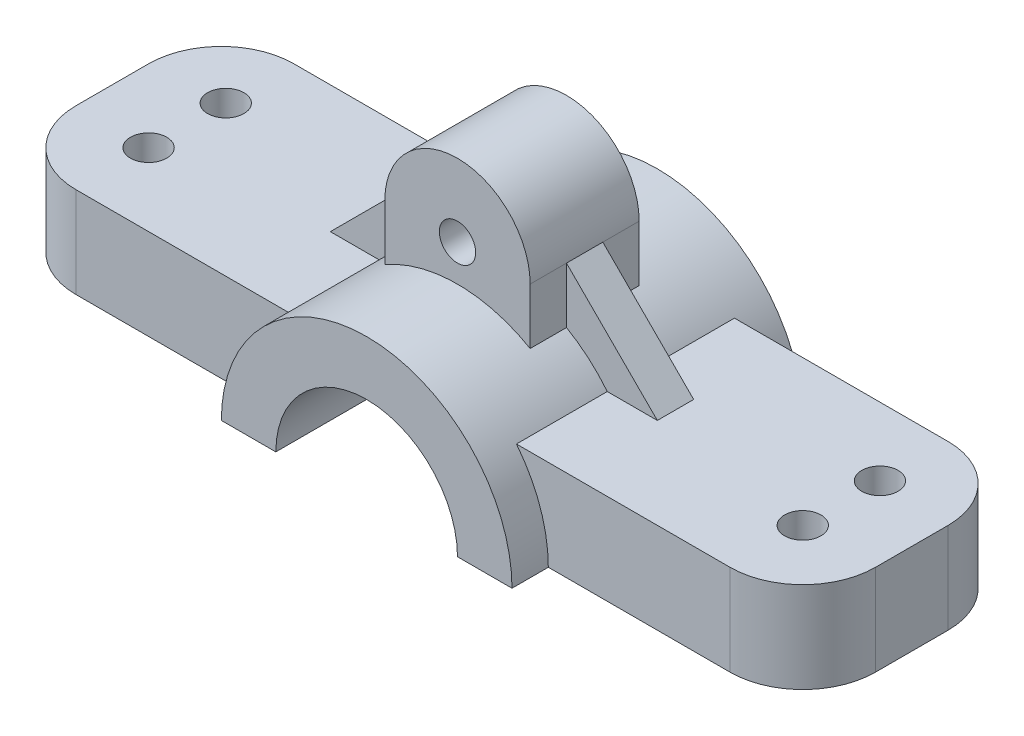
SolidWorks part; units mm, degrees
ref_plane "Front Plane" through (0, 0, 0) normal (0, 0, 1) x (1, 0, 0)
ref_plane "Top Plane" through (0, 0, 0) normal (0, 1, 0) x (1, 0, 0)
ref_plane "Right Plane" through (0, 0, 0) normal (1, 0, 0) x (0, 0, -1)
sketch "Sketch2" plane through (0, 0, 0) normal (0, 0, 1) x (1, 0, 0)
  line L0 (-40, 0) -> (-25, 0)
  line L1 (25, 0) -> (40, 0)
  arc A0 (40, 0) -> (-40, 0) centre (0, 0) ccw
  arc A1 (25, 0) -> (-25, 0) centre (0, 0) ccw
extrude "Boss-Extrude1" add sketch "Sketch2" along normal mid plane 80
sketch "Sketch3" plane through (0, 0, 0) normal (0, -1, 0) x (1, 0, 0)
  line L0 (0, 40.9906) -> (0, 0) construction
  line L1 (0, 0) -> (-81.2161, 0) construction
  line L8 (-10, 30) -> (-110.0261, 30)
  line L9 (-10, 30) -> (-10, -30)
  line L10 (-10, -30) -> (-110.0261, -30)
  line L11 (-110.0261, 30) -> (-110.0261, -30)
  point P4 (0, 0)
  dimension "D1" = 10
  dimension "D2" = 60
  dimension "D3" = 60
extrude "Boss-Extrude2" add sketch "Sketch3" against normal blind 25
fillet "Fillet1" radius 20 2 edges at (-110.0261, 12.5, -30) (-110.0261, 12.5, 30)
hole_wizard "Ø10.0 (10) Diameter Hole1" positions "Sketch15" profile "Sketch14" hole size "Ø10.0" standard "ANSI Metric" end condition through all
sketch "Sketch15" plane through (0, 25, 0) normal (0, 1, 0) x (1, 0, 0)
  point P0 (-90.0261, -10)
  point P3 (-90.0261, 11.2379)
sketch "Sketch14" plane through (-90.0261, 25, 10) normal (1, 0, 0) x (0, 0, 1)
  line L0 (0, 0) -> (0, 25)
  line L1 (0, 25) -> (5, 25)
  line L2 (5, 25) -> (5, 0)
  line L5 (5, 0) -> (0, 0)
  line L11 (0, -6.35) -> (0, 107.95) construction
  dimension "Thru Hole Dia." = 10
  dimension "Thru Hole Depth" = 25
mirror "Mirror1" about plane through (0, 0, 0) normal (1, 0, 0) of "Ø10.0 (10) Diameter Hole1", "Fillet1", "Boss-Extrude2"
other "DeleteFace1" face at (-10, 11.4564, 0) face at (-16.1388, 8.3832, 30) face at (-16.1388, 8.3832, -30) face at (16.1388, 8.3832, 30) face at (10, 11.4564, 0) face at (16.1388, 8.3832, -30) and patch yes
sketch "Sketch16" plane through (0, 0, 0) normal (0, 0, 1) x (1, 0, 0)
  line L0 (-20, 50) -> (-20, 34.641)
  line L1 (20, 50) -> (20, 34.641)
  line L4 (25, 0) -> (40, 0)
  line L5 (-40, 0) -> (-25, 0)
  line L6 (25, 0) -> (40, 0)
  line L7 (-40, 0) -> (-25, 0)
  arc A0 (20, 50) -> (-20, 50) centre (0, 50) ccw
  circle A1 centre (0, 50) radius 5
  arc A2 (40, 0) -> (-40, 0) centre (0, 0) ccw construction
  arc A5 (25, 0) -> (-25, 0) centre (0, 0) ccw
  arc A6 (40, 0) -> (-40, 0) centre (0, 0) ccw
  arc A7 (25, 0) -> (-25, 0) centre (0, 0) ccw
  arc A8 (20, 34.641) -> (-20, 34.641) centre (0, 0) ccw
  dimension "D1" = 50
  dimension "D2" = 0
extrude "Boss-Extrude3" add sketch "Sketch16" along normal mid plane 30 contours A8 L1 A0 L0 A1 region at (0, 69.4661, 0)
sketch "Sketch18" plane through (0, 0, 0) normal (0, 0, 1) x (1, 0, 0)
  line L0 (-20, 50) -> (-45, 25)
  line L1 (-31.225, 25) -> (-90.0261, 25) construction
  dimension "D1" = 45
  dimension "D2" = 50
rib "Rib1" sketch "Sketch18" sketch "Sketch18" thickness 10 extrusion direction parallel to sketch draft on no parameters "D1"=10
mirror "Mirror2" about plane through (0, 0, 0) normal (1, 0, 0) of "Rib1"
